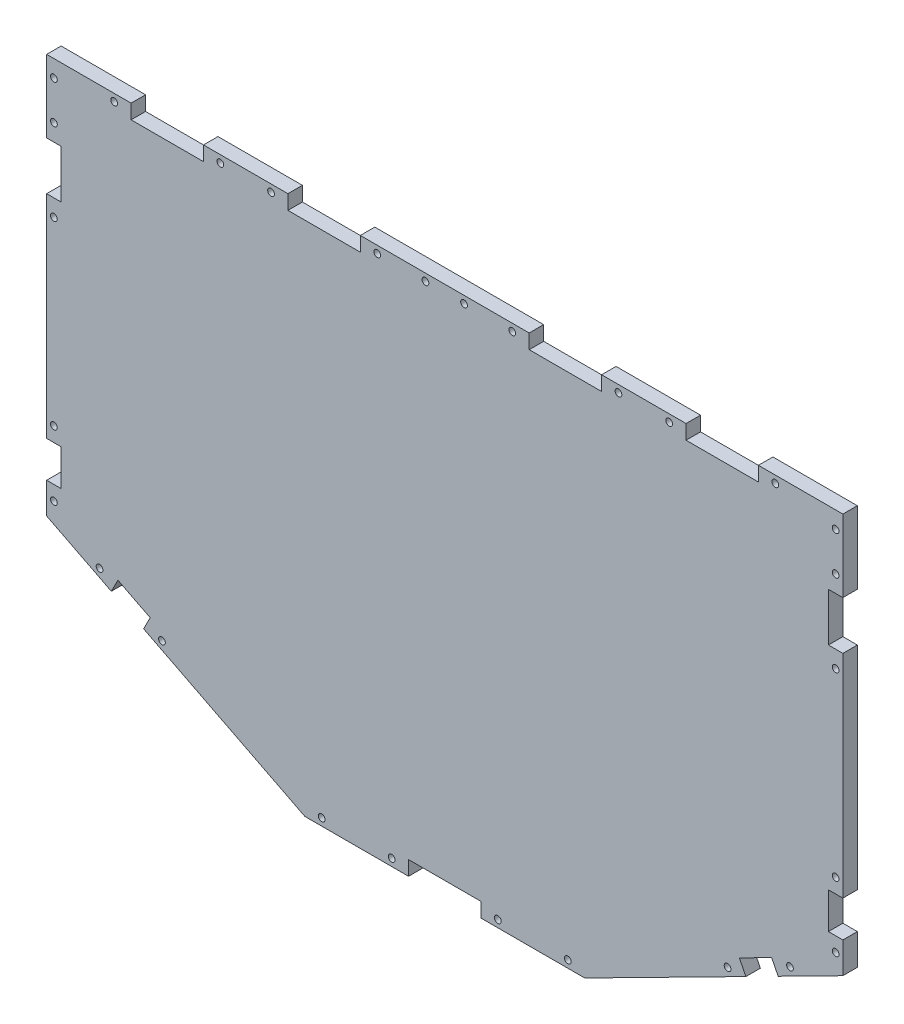
SolidWorks part; units mm, degrees
ref_plane "Plan de face" through (0, 0, 0) normal (0, 0, 1) x (1, 0, 0)
ref_plane "Plan de dessus" through (0, 0, 0) normal (0, 1, 0) x (1, 0, 0)
ref_plane "Plan de droite" through (0, 0, 0) normal (1, 0, 0) x (0, 0, -1)
sketch "Esquisse1" plane through (0, 0, 0) normal (0, 0, 1) x (1, 0, 0)
  line L0 (0, 124.9429) -> (0, -204.46) construction
  line L1 (-165, 110.0116) -> (165, 110.0116)
  line L2 (165, 110.0116) -> (165, -55.6884)
  line L3 (165, -55.6884) -> (58, -110.0116)
  line L4 (58, -110.0116) -> (-58, -110.0116)
  line L5 (-211.9802, 0) -> (248.5953, 0) construction
  line L6 (-58, -110.0116) -> (-165, -55.6884)
  line L7 (-165, -55.6884) -> (-165, 110.0116)
  dimension "D1" = 330
  dimension "D2" = 165
  dimension "D3" = 165.7
  dimension "D4" = 165.7
  dimension "D5" = 120
  dimension "D6" = 120
  dimension "D7" = 116
  dimension "D8" = 220.0231
  dimension "D9" = 110.0116
extrude "Boss.-Extru.1" add sketch "Esquisse1" along normal blind 6
sketch "Esquisse8" plane through (0, 0, 6) normal (0, 0, 1) x (1, 0, 0)
  line L0 (-165, 110.0116) -> (-165, -55.6884) construction
  line L1 (-165, -42.8484) -> (-159, -42.8484)
  line L2 (-165, -42.8484) -> (-165, -27.8484)
  line L3 (-165, -27.8484) -> (-159, -27.8484)
  line L4 (-159, -42.8484) -> (-159, -27.8484)
  line L5 (165, 110.0116) -> (-165, 110.0116) construction
  line L6 (-165, 60.0116) -> (-159, 60.0116)
  line L7 (-165, 60.0116) -> (-165, 80.0116)
  line L8 (-165, 80.0116) -> (-159, 80.0116)
  line L9 (-159, 60.0116) -> (-159, 80.0116)
  line L10 (-130, 110.0116) -> (-100, 110.0116)
  line L11 (-130, 110.0116) -> (-130, 104.0116)
  line L12 (-130, 104.0116) -> (-100, 104.0116)
  line L13 (-100, 110.0116) -> (-100, 104.0116)
  line L14 (0, 123.4485) -> (0, -147.0642) construction
  line L15 (-65, 110.0116) -> (-35, 110.0116)
  line L16 (-65, 110.0116) -> (-65, 104.0116)
  line L17 (-65, 104.0116) -> (-35, 104.0116)
  line L18 (-35, 110.0116) -> (-35, 104.0116)
  line L19 (159, -42.8484) -> (159, -27.8484)
  line L20 (165, -27.8484) -> (159, -27.8484)
  line L21 (165, -42.8484) -> (165, -27.8484)
  line L22 (165, -42.8484) -> (159, -42.8484)
  line L23 (35, 110.0116) -> (35, 104.0116)
  line L24 (65, 104.0116) -> (35, 104.0116)
  line L25 (65, 110.0116) -> (65, 104.0116)
  line L26 (65, 110.0116) -> (35, 110.0116)
  line L27 (100, 110.0116) -> (100, 104.0116)
  line L28 (130, 104.0116) -> (100, 104.0116)
  line L29 (130, 110.0116) -> (130, 104.0116)
  line L30 (130, 110.0116) -> (100, 110.0116)
  line L31 (159, 60.0116) -> (159, 80.0116)
  line L32 (165, 80.0116) -> (159, 80.0116)
  line L33 (165, 60.0116) -> (165, 80.0116)
  line L34 (165, 60.0116) -> (159, 60.0116)
  line L35 (-58, -110.0116) -> (58, -110.0116) construction
  line L36 (-15, -110.0116) -> (15, -110.0116)
  line L37 (-15, -110.0116) -> (-15, -104.0116)
  line L38 (-15, -104.0116) -> (15, -104.0116)
  line L39 (15, -110.0116) -> (15, -104.0116)
  line L41 (-138.1876, -69.3009) -> (-124.8126, -76.0913)
  line L42 (-138.1876, -69.3009) -> (-135.4714, -63.9509)
  line L43 (-124.8126, -76.0913) -> (-122.0964, -70.7413)
  line L44 (-135.4714, -63.9509) -> (-122.0964, -70.7413)
  line L45 (-165, -55.6884) -> (-58, -110.0116) construction
  line L46 (135.4714, -63.9509) -> (122.0964, -70.7413)
  line L47 (124.8126, -76.0913) -> (122.0964, -70.7413)
  line L48 (138.1876, -69.3009) -> (135.4714, -63.9509)
  line L49 (138.1876, -69.3009) -> (124.8126, -76.0913)
  dimension "D1" = 6
  dimension "D2" = 15
  dimension "D3" = 12.84
  dimension "D4" = 6
  dimension "D5" = 6
  dimension "D6" = 20
  dimension "D7" = 30
  dimension "D8" = 30
  dimension "D9" = 6
  dimension "D10" = 35
  dimension "D11" = 35
  dimension "D12" = 30
  dimension "D13" = 30
  dimension "D14" = 6
  dimension "D15" = 43
  dimension "D16" = 6
  dimension "D17" = 15
  dimension "D18" = 30.07
extrude "Enlèv. mat.-Extru.2" cut sketch "Esquisse8" against normal blind 6
sketch "Esquisse9" plane through (0, 0, 6) normal (0, 0, 1) x (1, 0, 0)
  line L0 (0, 149.6894) -> (0, -144.2465) construction
  line L1 (35, 110.0116) -> (-35, 110.0116) construction
  line L2 (-65, 110.0116) -> (-100, 110.0116) construction
  line L3 (-35, 104.0116) -> (-35, 110.0116) construction
  line L4 (-65, 110.0116) -> (-65, 104.0116) construction
  line L5 (-100, 104.0116) -> (-100, 110.0116) construction
  line L6 (-130, 110.0116) -> (-130, 104.0116) construction
  line L7 (-130, 110.0116) -> (-165, 110.0116) construction
  line L8 (-165, 110.0116) -> (-165, 80.0116) construction
  line L9 (-159, 80.0116) -> (-165, 80.0116) construction
  line L10 (-165, 60.0116) -> (-159, 60.0116) construction
  line L11 (-165, 60.0116) -> (-165, -27.8484) construction
  line L12 (-159, -27.8484) -> (-165, -27.8484) construction
  line L13 (-165, -42.8484) -> (-165, -55.6884) construction
  line L14 (-165, -42.8484) -> (-159, -42.8484) construction
  line L15 (-58, -110.0116) -> (-15, -110.0116) construction
  line L16 (-15, -104.0116) -> (-15, -110.0116) construction
  line L18 (-124.8126, -76.0913) -> (-122.0964, -70.7413) construction
  line L19 (-135.4714, -63.9509) -> (-138.1876, -69.3009) construction
  line L20 (-165, -55.6884) -> (-138.1876, -69.3009) construction
  line L21 (-124.8126, -76.0913) -> (-58, -110.0116) construction
  circle A0 centre (-162, -48.8484) radius 1.4
  circle A1 centre (-162, -21.8484) radius 1.4
  circle A2 centre (-162, 53.0116) radius 1.4
  circle A3 centre (-162, 87.0116) radius 1.4
  circle A4 centre (-162, 103.0116) radius 1.4
  circle A5 centre (-137, 107.0116) radius 1.4
  circle A6 centre (-93, 107.0116) radius 1.4
  circle A7 centre (-72, 107.0116) radius 1.4
  circle A8 centre (-28, 107.0116) radius 1.4
  circle A9 centre (-8, 107.0116) radius 1.4
  circle A10 centre (8, 107.0116) radius 1.4
  circle A11 centre (28, 107.0116) radius 1.4
  circle A12 centre (72, 107.0116) radius 1.4
  circle A13 centre (93, 107.0116) radius 1.4
  circle A14 centre (137, 107.0116) radius 1.4
  circle A15 centre (162, 103.0116) radius 1.4
  circle A16 centre (162, 87.0116) radius 1.4
  circle A17 centre (162, 53.0116) radius 1.4
  circle A18 centre (162, -21.8484) radius 1.4
  circle A19 centre (162, -48.8484) radius 1.4
  circle A20 centre (-51, -107.0116) radius 1.4
  circle A21 centre (-22, -107.0116) radius 1.4
  circle A22 centre (22, -107.0116) radius 1.4
  circle A23 centre (51, -107.0116) radius 1.4
  circle A24 centre (-143.0712, -63.4571) radius 1.4
  circle A25 centre (-117.2128, -76.5851) radius 1.4
  circle A26 centre (117.2128, -76.5851) radius 1.4
  circle A27 centre (143.0712, -63.4571) radius 1.4
  point P29 (-65, 107.0116)
  point P42 (-162, 60.0116)
  point P93 (-136.8295, -66.6259)
  dimension "D1" = 2.8
  dimension "D2" = 2.8
  dimension "D3" = 2.8
  dimension "D4" = 3
  dimension "D5" = 3
  dimension "D7" = 2.8
  dimension "D8" = 20
  dimension "D9" = 3
  dimension "D10" = 7
  dimension "D11" = 7
  dimension "D12" = 3
  dimension "D13" = 2.8
  dimension "D14" = 7
  dimension "D15" = 3
  dimension "D16" = 7
  dimension "D17" = 2.8
  dimension "D18" = 3
  dimension "D19" = 3
  dimension "D20" = 7
  dimension "D21" = 2.8
  dimension "D22" = 2.8
  dimension "D23" = 7
  dimension "D24" = 3
  dimension "D25" = 2.8
  dimension "D26" = 3
  dimension "D27" = 6
  dimension "D28" = 2.8
  dimension "D29" = 3
  dimension "D30" = 6
  dimension "D31" = 2.8
  dimension "D32" = 2.8
  dimension "D33" = 3
  dimension "D34" = 3
  dimension "D35" = 7
  dimension "D36" = 7
  dimension "D37" = 2.8
  dimension "D38" = 2.8
  dimension "D39" = 7
  dimension "D40" = 7
  dimension "D41" = 3
  dimension "D42" = 3
  dimension "D6" = 7
extrude "Enlèv. mat.-Extru.3" cut sketch "Esquisse9" against normal blind 6
equation "\"D2@Esquisse1\"=\"D1@Esquisse1\"/2"
equation "\"D9@Esquisse1\"=\"D8@Esquisse1\"/2"
